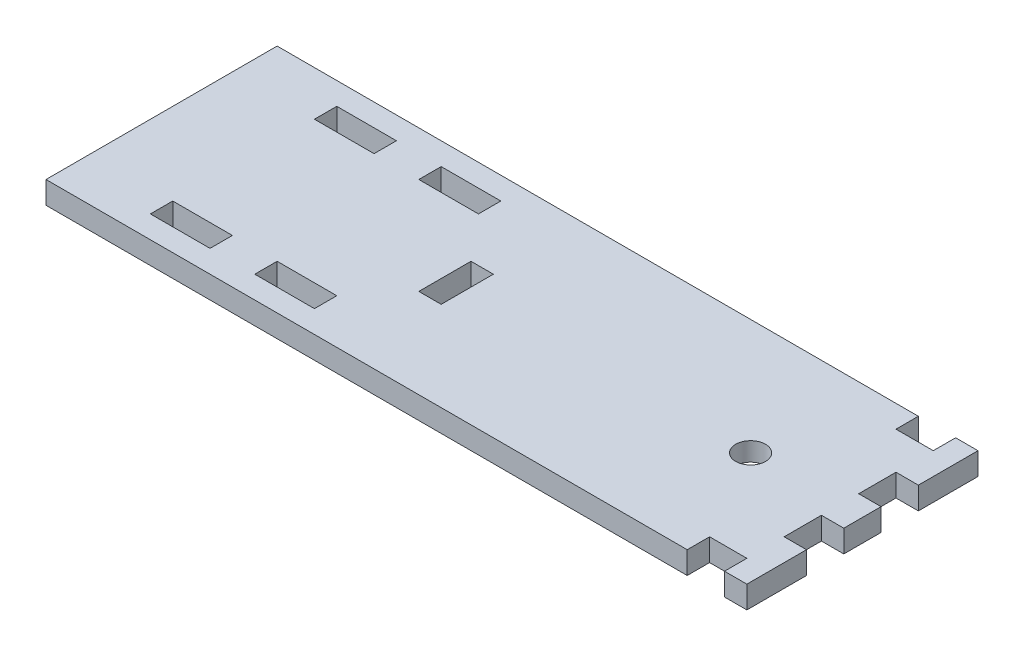
SolidWorks part; units mm, degrees
ref_plane "Front Plane" through (0, 0, 0) normal (0, 0, 1) x (1, 0, 0)
ref_plane "Top Plane" through (0, 0, 0) normal (0, 1, 0) x (1, 0, 0)
ref_plane "Right Plane" through (0, 0, 0) normal (1, 0, 0) x (0, 0, -1)
sketch "Sketch1" plane through (0, 0, 0) normal (0, 1, 0) x (1, 0, 0)
  line L1 (-94, 31) -> (94, 31)
  line L2 (-94, 31) -> (-94, -31)
  line L3 (-94, -31) -> (94, -31)
  line L4 (94, 31) -> (94, -31)
  line L5 (-94, 31) -> (94, -31) construction
  line L6 (-94, -31) -> (94, 31) construction
  point P0 (0, 0)
  dimension "D2" = 62
  dimension "D1" = 188
sketch "Sketch2" plane through (0, 0, 0) normal (0, 0, 1) x (1, 0, 0)
  line L0 (0, 0) -> (0, 6) construction
  line L1 (-94, 0) -> (94, 0) construction
  dimension "D1" = 6
extrude "Boss-Extrude1" add sketch "Sketch1" along normal up to vertex (6 mm away) contours L2 L3 L4 L1 up to point (0, 6, 0)
sketch "Sketch3" plane through (0, 0, 0) normal (0, -1, 0) x (1, 0, 0)
  line L0 (64, 0) -> (94, 0)
  line L1 (94, -31) -> (94, 31) construction
  circle A0 centre (64, 0) radius 4
  dimension "D1" = 8
  dimension "D2" = 30
extrude "Cut-Extrude1" cut sketch "Sketch3" against normal through all contours A0 region at (60.1131, 0, 0)
sketch "Sketch5" plane through (0, 6, 0) normal (0, 1, 0) x (1, 0, 0)
  line L0 (94, 31) -> (94, -31) construction
  line L1 (94, -31) -> (88, -31)
  line L2 (94, -31) -> (94, -25)
  line L3 (94, -25) -> (88, -25)
  line L4 (88, -31) -> (88, -25)
  line L5 (88, -25) -> (94, -25)
  line L6 (88, -25) -> (88, -15)
  line L7 (88, -15) -> (94, -15)
  line L8 (94, -25) -> (94, -15)
  line L9 (-94, 31) -> (94, 31) construction
  line L10 (94, -15) -> (88, -15)
  line L11 (94, -15) -> (94, -5)
  line L12 (94, -5) -> (88, -5)
  line L13 (88, -15) -> (88, -5)
  line L14 (88, -5) -> (94, -5)
  line L15 (88, -5) -> (88, 5)
  line L16 (88, 5) -> (94, 5)
  line L17 (94, -5) -> (94, 5)
  line L18 (94, 5) -> (88, 5)
  line L19 (94, 5) -> (94, 15)
  line L20 (94, 15) -> (88, 15)
  line L21 (88, 5) -> (88, 15)
  line L22 (88, 15) -> (94, 15)
  line L23 (88, 15) -> (88, 25)
  line L24 (88, 25) -> (94, 25)
  line L25 (94, 15) -> (94, 25)
  line L26 (94, 25) -> (88, 25)
  line L27 (94, 25) -> (94, 31)
  line L28 (94, 31) -> (88, 31)
  line L29 (88, 25) -> (88, 31)
  point P21 (94, 15.7339)
  line M33 (94, -31) -> (94, 31)
  dimension "D1" = 6
  dimension "D2" = 6
  dimension "D3" = 10
extrude "Cut-Extrude2" cut sketch "Sketch5" against normal through all contours L13 L7 L12 M33 | L21 L16 L20 M33 region at (91, 6, 10) region at (91, 6, -10)
sketch "Sketch6" plane through (0, 0, 0) normal (0, -1, 0) x (1, 0, 0)
  line L0 (88, 31) -> (88, 25) construction
  line L1 (78, 25) -> (88, 25)
  line L2 (78, 25) -> (78, 31)
  line L3 (78, 31) -> (88, 31)
  line L4 (88, 25) -> (88, 31)
  line L5 (-94, 31) -> (94, 31) construction
  line L7 (-18, -7) -> (-12, -7)
  line L8 (-18, -7) -> (-18, 7)
  line L9 (-18, 7) -> (-12, 7)
  line L10 (-12, -7) -> (-12, 7)
  line L11 (-28, 19) -> (-44, 19)
  line L12 (-28, 19) -> (-28, 25)
  line L13 (-28, 25) -> (-44, 25)
  line L14 (-44, 19) -> (-44, 25)
  line L15 (-72, 19) -> (-56, 19)
  line L16 (-72, 19) -> (-72, 25)
  line L17 (-72, 25) -> (-56, 25)
  line L18 (-56, 19) -> (-56, 25)
extrude "Cut-Extrude3" cut sketch "Sketch6" against normal through all
mirror "Mirror1" about plane through (0, 0, 0) normal (0, 0, 1) of "Cut-Extrude3"
sketch "Sketch7" plane through (0, 0, 0) normal (0, -1, 0) x (-1, 0, 0)
  line L0 (-68, 0) -> (-72, 0) construction
  line L1 (-68, -5) -> (-68, 5) construction
  line L2 (-45, -27) -> (-45, -31) construction
  line L3 (94, -31) -> (-78, -31) construction
  line L4 (-26, 0) -> (-64, 0) construction
  line L5 (-45, -19) -> (-45, 19) construction
  line L6 (-26, 5) -> (-26, -5) construction
  line L7 (-24, 5) -> (-24, -5)
  line L8 (-28, 5) -> (-28, -5)
  line L9 (-45, 13.8035) -> (-45, 24.1965) construction
  line L10 (-50.1965, 19) -> (-39.8035, 19) construction
  circle A0 centre (-45, 0) radius 27
  circle A1 centre (-64, 0) radius 4 construction
  circle A2 centre (-64, 0) radius 4
  circle A3 centre (-45, 0) radius 1
  arc A4 (-24, 5) -> (-28, 5) centre (-26, 5) ccw
  arc A5 (-28, -5) -> (-24, -5) centre (-26, -5) ccw
  circle A6 centre (-45, 24.1965) radius 1.25
  circle A7 centre (-39.8035, 19) radius 1.25
  circle A8 centre (-45, 13.8035) radius 1.25
  circle A9 centre (-50.1965, 19) radius 1.25
  point P17 (-45, 0)
  point P19 (-45, 0)
  point P21 (-26, 0)
  point P29 (-45, 19)
  point P32 (-45, 19)
  point P36 (-50.4683, 16.2)
  point P37 (-50.1965, 16.2)
  circle M17 centre (-64, 0) radius 4
  dimension "D3" = 2
  dimension "D6" = 2.5
  dimension "D1" = 4
  dimension "D2" = 4
  dimension "D4" = 4
  dimension "D5" = 10
extrude "Cut-Extrude4" cut sketch "Sketch7" against normal blind 1 contours A0 A9 A8 A7 A6 A5 L8 A4 L7 A3 M17 region at (71.2363, 0, 0)
equation "\"glass_width\"= 150"
equation "\"glass_height\"= 100"
equation "\"glass_thickness\"= 4"
equation "\"brood_space\"= 42"
equation "\"t1\"= 6"
equation "\"t2\"= 6"
equation "\"box_depth\"= \"brood_space\" + \"glass_thickness\" + \"glass_thickness\" + \"t2\" + \"t2\""
equation "\"box_width\"= \"glass_width\" + \"t1\" + \"t1\""
equation "\"food_height\"= 70"
equation "\"box_height\"= \"glass_height\" + ( \"t1\" * 3 ) + \"food_height\""
equation "\"D1@Sketch2\"= \"t1\""
equation "\"entry_height\"= 24"
equation "\"entry_diameter\"= 8"
equation "\"food_top_clearance\"= 10"
equation "\"bar_width\"= 20"
equation "\"glassblocker_lower_height\"= 10"
equation "\"D2@Sketch1\"=\"box_depth\""
equation "\"D1@Sketch1\"=\"box_height\""
equation "\"D1@Sketch3\"=\"entry_diameter\""
equation "\"D2@Sketch3\"=\"entry_height\" + \"t1\""
equation "\"D1@Sketch5\"=\"t1\""
equation "\"D2@Sketch5\"=\"t2\""
